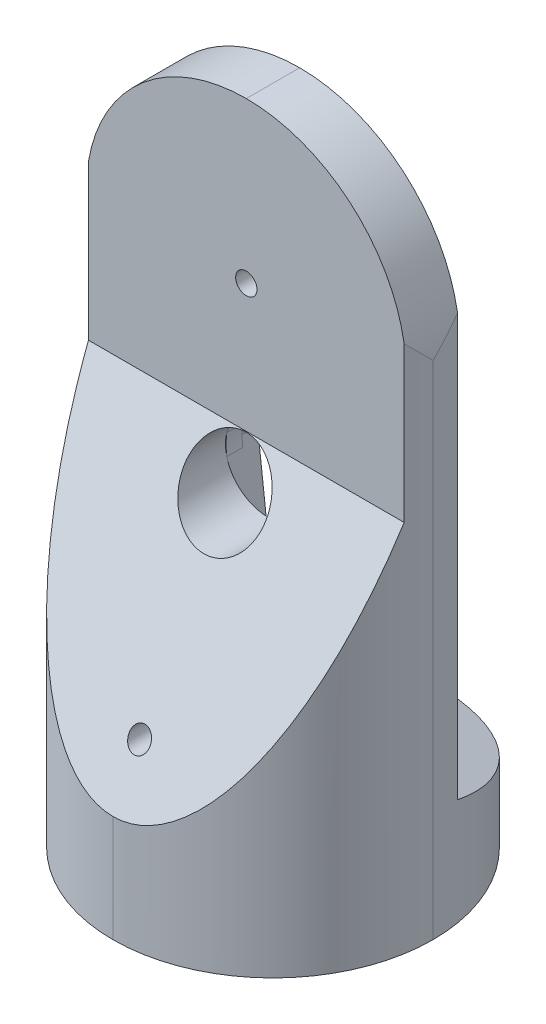
SolidWorks part; units mm, degrees
ref_plane "Front Plane" through (0, 0, 0) normal (0, 0, 1) x (1, 0, 0)
ref_plane "Top Plane" through (0, 0, 0) normal (0, 1, 0) x (1, 0, 0)
ref_plane "Right Plane" through (0, 0, 0) normal (1, 0, 0) x (0, 0, -1)
sketch "Sketch1" plane through (0, 0, 0) normal (0, 0, 1) x (1, 0, 0)
  line L0 (-2.1, 16) -> (-3.95, 0)
  line L1 (-15, -31) -> (15, -31)
  line L2 (-15, -31) -> (-15, 31)
  line L3 (-15, 31) -> (15, 31)
  line L4 (15, -31) -> (15, 31)
  line L5 (-15, -31) -> (-3.1882, -6.5889) construction
  line L6 (-15, 31) -> (-3.1882, 6.5889) construction
  line L7 (0, 31) -> (0, 18.1) construction
  line L8 (-15, 0) -> (-3.95, 0) construction
  line L9 (2.1, 16) -> (3.95, 0)
  line L10 (2.1, -16) -> (3.95, 0)
  line L11 (-2.1, -16) -> (-3.95, 0)
  line L12 (3.95, 0) -> (15, 0) construction
  line L13 (3.1882, -6.5889) -> (15, -31) construction
  line L14 (3.1882, 6.5889) -> (15, 31) construction
  line L15 (0, -18.1) -> (0, -31) construction
  arc A0 (-3.8458, 0.9014) -> (-3.8458, -0.9014) centre (0, 0) ccw
  arc A1 (2.1, 16) -> (-2.1, 16) centre (0, 16) ccw
  arc A2 (2.1, -16) -> (-2.1, -16) centre (0, -16) cw
  arc A3 (3.8458, -0.9014) -> (3.8458, 0.9014) centre (0, 0) ccw
  circle A4 centre (0, 16) radius 1
  circle A5 centre (0, -16) radius 1
  point P0 (0, 0)
  dimension "D1" = 7.9
  dimension "D2" = 4.2
  dimension "D4" = 15
  dimension "D5" = 15
  dimension "D6" = 2
  dimension "D7" = 2
  dimension "D3" = 36.2
sketch "Sketch2" plane through (0, 0, 0) normal (0, 0, 1) x (1, 0, 0)
  line L1 (-15, -31) -> (15, -31)
  line L2 (-15, -31) -> (-15, 31)
  line L3 (-15, 31) -> (15, 31)
  line L4 (15, -31) -> (15, 31)
  line L5 (-15, -31) -> (15, 31) construction
  line L6 (-15, 31) -> (15, -31) construction
  point P0 (0, 0)
  dimension "D1" = 62
extrude "Boss-Extrude10" add sketch "Sketch2" along normal blind 5
extrude "Cut-Extrude5" cut sketch "Sketch1" along normal blind 1.5 contours A2 L10 L9 A1 L0 L11 A5 A4 region at (0, 0, 0)
extrude "Cut-Extrude6" cut sketch "Sketch1<14>" along normal through all contours A4 | A5
sketch "Sketch1<14>" plane through (0, 0, 0) normal (0, 0, 1) x (1, 0, 0) same geometry as "Sketch1"
fillet "Fillet1" radius 15 2 edges at (-15, 31, 2.5) (15, 31, 2.5)
sketch "Sketch5" plane through (0, 0, 0) normal (0, 0, -1) x (-1, 0, 0)
  line L0 (15, 16) -> (15, -31) construction
  line L1 (-15, -31) -> (15, -31)
  line L2 (-15, -31) -> (-15, -26)
  line L3 (-15, -26) -> (15, -26)
  line L4 (15, -31) -> (15, -26)
  dimension "D1" = 5
extrude "Boss-Extrude11" add sketch "Sketch5" along normal blind 12.5
ref_plane "Plane1" through (0, 0, 2.5) normal (0, 0, 1) x (1, 0, 0)
mirror "Mirror1" about plane through (0, 0, 2.5) normal (0, 0, 1) of "Boss-Extrude11"
fillet "Fillet2" radius 15 4 edges at (15, -28.5, 17.5) (-15, -28.5, 17.5) (-15, -28.5, -12.5) (15, -28.5, -12.5)
sketch "Sketch7" plane through (0, -31, 0) normal (0, -1, 0) x (1, 0, 0)
  circle A0 centre (0, 2.5) radius 2.5
  arc A1 (15, 2.5) -> (0, 17.5) centre (0, 2.5) ccw construction
  dimension "5" = 5
extrude "Cut-Extrude7" cut sketch "Sketch7" against normal blind 3
chamfer "Chamfer1" distance 15 distance2 30 1 edges at (0, -26, 5) first distance on face at (0, -26, 10.971)
chamfer "Chamfer2" distance 5 distance2 15 1 edges at (0, -26, 0) first distance on face at (0, 4.2826, 0)
sketch "Sketch8" plane through (0, 0, 1.5) normal (0, 0, -1) x (-1, 0, 0)
  line L0 (-3.3141, -5.5) -> (3.3141, -5.5)
  line L1 (-2.1, -16) -> (-3.95, 0) construction
  line L2 (2.1, -16) -> (3.95, 0) construction
  line L3 (-3.3141, 5.5) -> (3.3141, 5.5)
  line L4 (-2.1, 16) -> (-3.95, 0) construction
  line L5 (2.1, 16) -> (3.95, 0) construction
  line L6 (-3.3141, 5.5) -> (-3.8371, 0.9763)
  line L7 (-2.1, -16) -> (-3.95, 0) construction
  line L8 (-3.8371, -0.9763) -> (-3.3141, -5.5)
  line L9 (3.3141, 5.5) -> (3.8371, 0.9763)
  line L11 (3.8371, -0.9763) -> (3.3141, -5.5)
  arc A0 (-3.8371, 0.9763) -> (-3.8371, -0.9763) centre (4.6066, 0) ccw
  arc A1 (3.8371, 0.9763) -> (3.8371, -0.9763) centre (-4.6066, 0) cw
  dimension "D3" = 8.5
  dimension "D1" = 11
  dimension "D2" = 5.5
extrude "Cut-Extrude8" cut sketch "Sketch8" against normal blind 1.5
sketch "Sketch9" plane through (0, 0, 3) normal (0, 0, -1) x (-1, 0, 0)
  circle A0 centre (0, 0) radius 3.95
extrude "Cut-Extrude9" cut sketch "Sketch9" against normal blind 10
